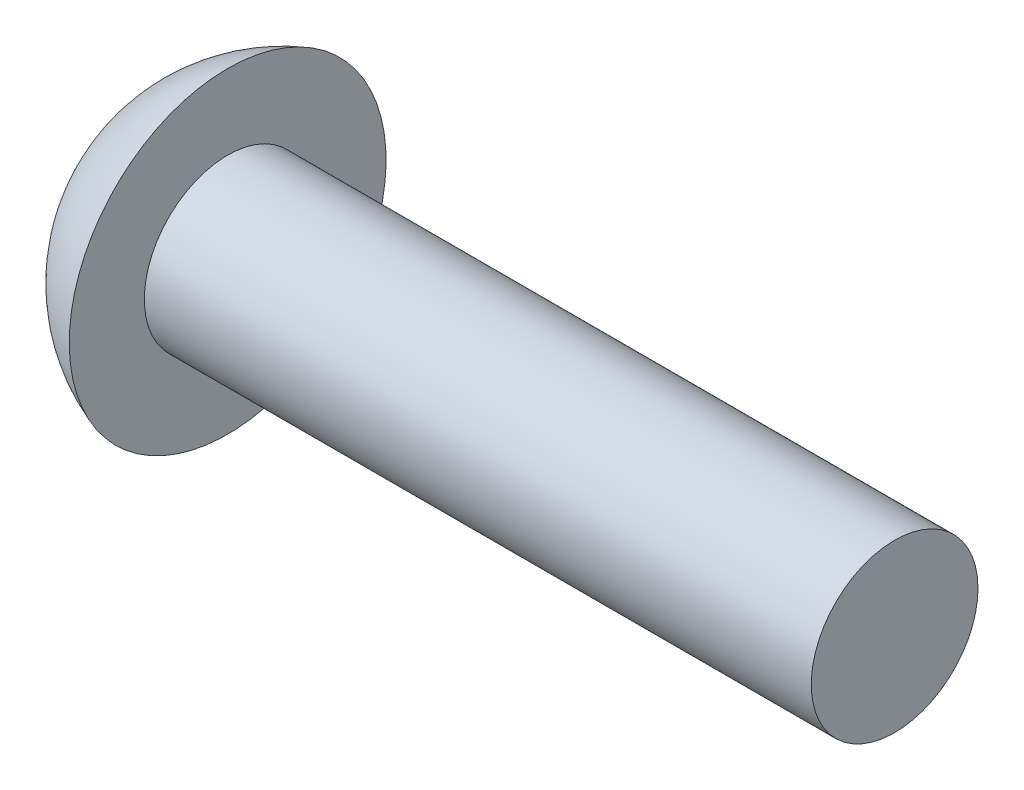
SolidWorks part; units mm, degrees
ref_plane "Front" through (0, 0, 0) normal (0, 0, 1) x (1, 0, 0)
ref_plane "Top" through (0, 0, 0) normal (0, 1, 0) x (1, 0, 0)
ref_plane "Right" through (0, 0, 0) normal (1, 0, 0) x (0, 0, -1)
other "Configuration Table"
sketch "Sketch1" plane through (0, 0, 0) normal (1, 0, 0) x (0, 0, -1)
  line L0 (0, 0) -> (1.4, 0) construction
  circle A0 centre (0, 0) radius 3.8
extrude "BaseHead" add sketch "Sketch1" along normal blind 2.2
sketch "Sketch2" plane through (2.2, 0, 0) normal (1, 0, 0) x (0, 0, -1)
  circle A0 centre (0, 0) radius 2
extrude "BaseBody" add sketch "Sketch2" along normal blind 16
cosmetic thread "ThreadCosmetic1" parameters "D1"=14.6, "THD_MINOR"=3.242
fillet "HeadFillet" [suppressed] radius 0.2
sketch "Sketch3" plane through (-13.4796, 2.4796, 0) normal (0, 0, 1) x (0, -1, 0)
  line L0 (2.4796, 13.4796) -> (2.4796, 41.0387) construction
  line L3 (-1.3204, 13.4796) -> (2.4796, 13.4796) construction
  line L5 (-6.3204, 15.6796) -> (-6.3204, 8.4796)
  line L6 (0.5446, 13.4796) -> (0.5446, 8.4796)
  line L7 (0.5446, 8.4796) -> (-6.3204, 8.4796)
  line L8 (-6.3204, 15.6796) -> (-1.3204, 15.6796)
  line L9 (-1.3204, 13.4796) -> (6.2796, 13.4796) construction
  arc A0 (-1.3204, 15.6796) -> (0.5446, 13.4796) centre (2.4796, 17.0104) ccw
  dimension "D2" = 5
  dimension "e" = 3.87
  dimension "D3" = 5
revolve "Cut-Revolve1" cut sketch "Sketch3" angle 360 about L0
sketch "Sketch4" plane through (0, 0, 0) normal (1, 0, 0) x (0, 0, -1)
  line L1 (1.4434, 0) -> (0.7217, 1.25)
  line L2 (0.7217, 1.25) -> (-0.7217, 1.25)
  line L3 (-0.7217, 1.25) -> (-1.4434, 0)
  line L4 (-1.4434, 0) -> (-0.7217, -1.25)
  line L5 (-0.7217, -1.25) -> (0.7217, -1.25)
  line L6 (0.7217, -1.25) -> (1.4434, 0)
  circle A0 centre (0, 0) radius 1.25 construction
  dimension "s" = 2.5
extrude "HexagonSocket" cut sketch "Sketch4" along normal blind 1.3
sketch "Sketch5" plane through (1.3, 0, 0) normal (-1, 0, 0) x (0, 0, 1)
  line L0 (0.7217, -1.25) -> (-0.7217, -1.25) construction
  line L1 (-0.7217, -1.25) -> (-1.4434, 0) construction
  line L2 (1.4434, 0) -> (0.7217, -1.25) construction
  line L3 (0.7217, 1.25) -> (1.4434, 0) construction
  line L4 (-1.4434, 0) -> (-0.7217, 1.25) construction
  line L5 (-0.7217, 1.25) -> (0.7217, 1.25) construction
  line L6 (0.7217, -1.25) -> (-0.7217, -1.25)
  line L7 (-0.7217, -1.25) -> (-1.4434, 0)
  line L8 (1.4434, 0) -> (0.7217, -1.25)
  line L9 (0.7217, 1.25) -> (1.4434, 0)
  line L10 (-1.4434, 0) -> (-0.7217, 1.25)
  line L11 (-0.7217, 1.25) -> (0.7217, 1.25)
extrude "Cut-Extrude2" cut sketch "Sketch5" against normal blind 5 draft 60
sketch "Sketch6" plane through (0, 0, 0) normal (0, 0, 1) x (1, 0, 0)
  line L0 (18.2, 1.6718) -> (18.3895, 2)
  line L1 (18.3895, 2) -> (18.3895, 2.379)
  line L2 (18.3895, 2.379) -> (18.0105, 2.379)
  line L3 (18.0105, 2.379) -> (18.0105, 2)
  line L4 (18.0105, 2) -> (18.2, 1.6718)
  line L5 (0, 0) -> (24.7294, 0) construction
  line L6 (18.2, -2) -> (18.2, 2) construction
  dimension "D1" = 0.379
  dimension "D2" = 4
revolve "Cut-Revolve10" [suppressed] cut sketch "Sketch6" angle 360 about L5
pattern_linear "LPattern10" [suppressed] count 33 spacing 0.4548 along (-1, 0, 0) of bodies 106
equation "\"D1@ThreadCosmetic1\" = \"l@BaseBody\" - \"a@Sketch1\""
equation "\"D2@Sketch6\" = \"d@Sketch2\""
equation "\"D1@Sketch6\" =  (\"d@Sketch2\" - \"THD_MINOR@ThreadCosmetic1\" )  / 2"
equation "\"D3@LPattern10\" = \"D1@Sketch6\" * 1.2"
equation "\"D1@LPattern10\" = \"D1@ThreadCosmetic1\" / \"D3@LPattern10\" + 1"
